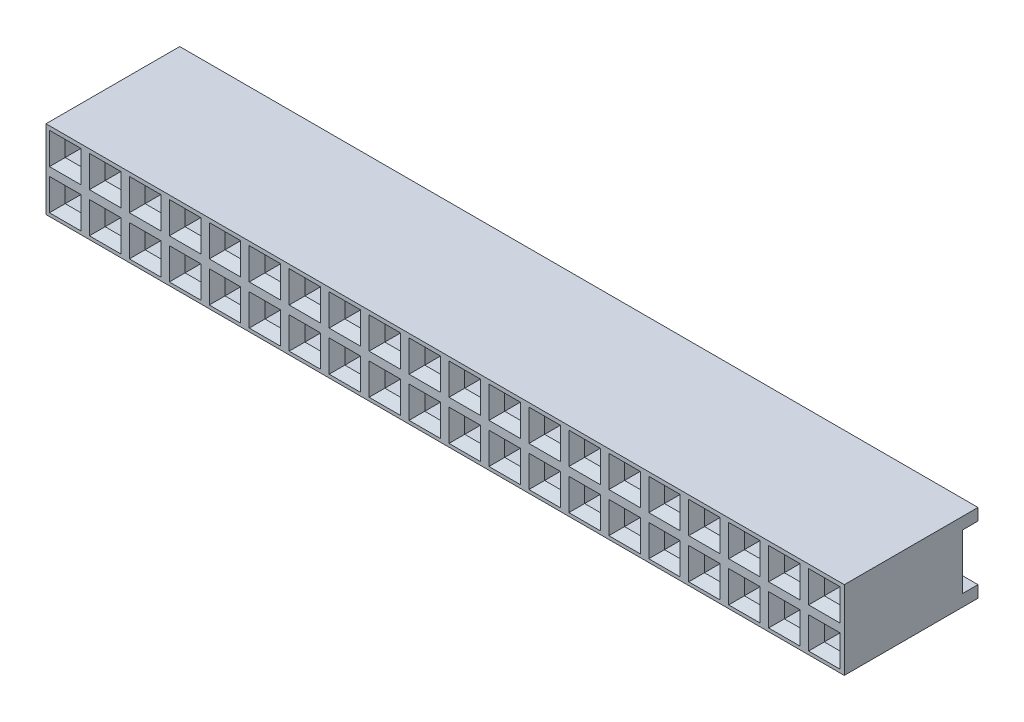
SolidWorks part; units mm, degrees
material "ABS"
ref_plane "Front Plane" through (0, 0, 0) normal (0, 0, 1) x (1, 0, 0)
ref_plane "Top Plane" through (0, 0, 0) normal (0, 1, 0) x (1, 0, 0)
ref_plane "Right Plane" through (0, 0, 0) normal (1, 0, 0) x (0, 0, -1)
sketch "Sketch1" plane through (0, 0, 0) normal (1, 0, 0) x (0, 0, -1)
  line L16 (8.5, 5) -> (0, 5)
  line L17 (0, 5) -> (0, 0)
  line L18 (0, 0) -> (8.5, 0)
  line L19 (8.5, 0) -> (8.5, 0.75)
  line L20 (8.5, 0.75) -> (7.5, 0.75)
  line L21 (7.5, 0.75) -> (7.5, 4.25)
  line L22 (7.5, 4.25) -> (8.5, 4.25)
  line L23 (8.5, 4.25) -> (8.5, 5)
  dimension "D1" = 3.5
  dimension "D2" = 0.75
  dimension "D3" = 1
  dimension "D4" = 8.5
  dimension "D5" = 5
extrude "Boss-Extrude1" add sketch "Sketch1" against normal blind 50.75 separate body
sketch "Sketch2" plane through (0, 0, -7.5) normal (0, 0, -1) x (-1, 0, 0)
  line L3 (2.27, 3.65) -> (2.27, 4.25)
  line L4 (2.27, 3.65) -> (0.27, 3.65)
  line L5 (0.27, 3.65) -> (0.27, 4.25)
  line L6 (2.27, 4.25) -> (0.27, 4.25)
  line L7 (50.75, 4.25) -> (0, 4.25) construction
  line L8 (0, 0.75) -> (0, 4.25) construction
  dimension "D1" = 0.6
  dimension "D2" = 0.27
  dimension "D3" = 2
extrude "Cut-Extrude1" cut sketch "Sketch2" against normal blind 5.5
sketch "Sketch3" plane through (0, 0, 0) normal (0, 0, -1) x (-1, 0, 0)
  line L4 (0.77, 4.25) -> (1.77, 4.25)
  line L5 (0.77, 3.25) -> (0.77, 4.25)
  line L6 (1.77, 3.25) -> (0.77, 3.25)
  line L7 (1.77, 4.25) -> (1.77, 3.25)
  line L8 (2.27, 4.25) -> (0.27, 4.25) construction
  line L9 (0, 0.75) -> (0, 4.25) construction
  dimension "D1" = 1
  dimension "D2" = 0.77
extrude "Cut-Extrude2" cut sketch "Sketch3" along normal blind 6
sketch "Sketch4" plane through (0, 0, 0) normal (0, 0, 1) x (1, 0, 0)
  line L8 (-2.27, 4.75) -> (-2.27, 2.75)
  line L9 (-2.27, 2.75) -> (-0.27, 2.75)
  line L10 (-0.27, 2.75) -> (-0.27, 4.75)
  line L11 (-0.27, 4.75) -> (-2.27, 4.75)
  line L12 (-2.27, 4.75) -> (-2.27, 2.75)
  line L13 (-2.27, 2.75) -> (-0.27, 2.75)
  line L14 (-0.27, 2.75) -> (-0.27, 4.75)
  line L15 (-0.27, 4.75) -> (-2.27, 4.75)
  dimension "D1" = 0.5
extrude "Cut-Extrude3" cut sketch "Sketch4" against normal blind 0.5 draft 45
pattern_linear "LPattern1" count 20 spacing 2.54 along (-1, 0, 0) count 2 spacing 2.54 along (0, -1, 0) of "Cut-Extrude2", "Cut-Extrude1", "Cut-Extrude3"
